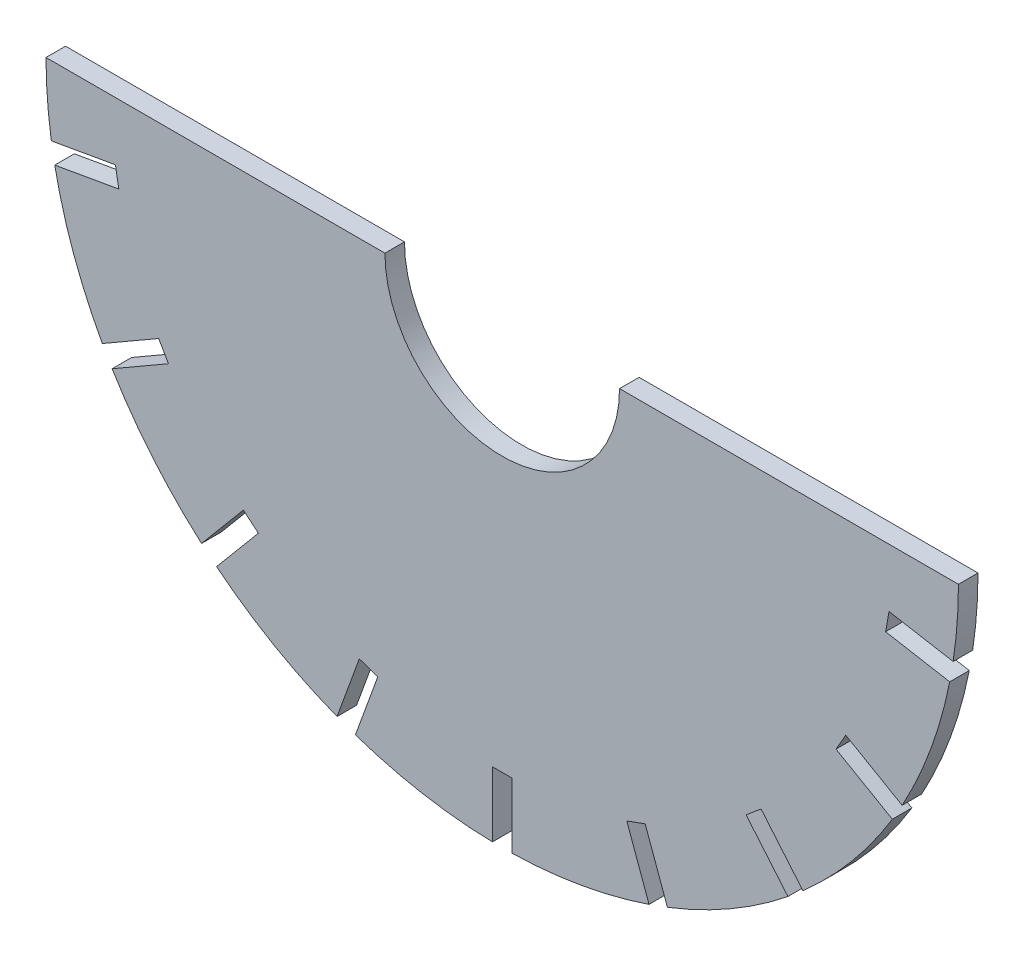
SolidWorks part; units mm, degrees
ref_plane "Front Plane" through (0, 0, 0) normal (0, 0, 1) x (1, 0, 0)
ref_plane "Top Plane" through (0, 0, 0) normal (0, 1, 0) x (1, 0, 0)
ref_plane "Right Plane" through (0, 0, 0) normal (1, 0, 0) x (0, 0, -1)
sketch "Sketch4" plane through (0, 0, 0) normal (0, 0, 1) x (1, 0, 0)
  line L1 (70, 0) -> (-70, 0)
  arc A0 (-70, 0) -> (70, 0) centre (0, 0) ccw
  dimension "D1" = 140
extrude "Boss-Extrude1" add sketch "Sketch4" along normal blind 3
sketch "Sketch5" plane through (0, 0, 0) normal (0, 0, 1) x (1, 0, 0)
  line L1 (-1.5, -60) -> (-1.5, -70)
  line L2 (-1.5, -60) -> (1.5, -60)
  line L4 (-1.5, -70) -> (1.5, -70)
  line L5 (1.5, -60) -> (1.5, -70)
extrude "Cut-Extrude2" cut sketch "Sketch5" along normal through all
ref_axis "Axis1" through (0, 0, 3) along (0, 0, -1)
pattern_circular "CirPattern1" count 5 every 20 about axis through (0, 0, 3) along (0, 0, -1) of "Cut-Extrude2" other way count 5
sketch "Sketch6" plane through (0, 0, 0) normal (0, 0, 1) x (1, 0, 0)
  circle A0 centre (0, 0) radius 18
  dimension "D1" = 36
extrude "Cut-Extrude3" cut sketch "Sketch6" along normal through all
